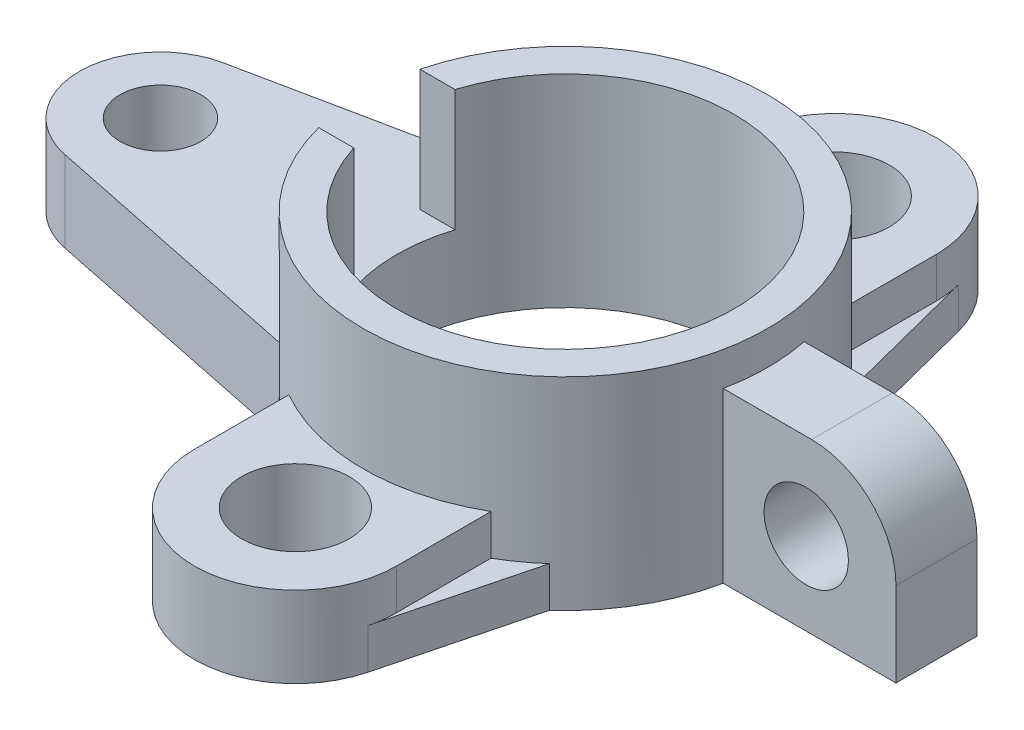
SolidWorks part; units mm, degrees
ref_plane "Ön Düzlem" through (0, 0, 0) normal (0, 0, 1) x (1, 0, 0)
ref_plane "Üst Düzlem" through (0, 0, 0) normal (0, 1, 0) x (1, 0, 0)
ref_plane "Sağ Düzlem" through (0, 0, 0) normal (1, 0, 0) x (0, 0, -1)
sketch "Çizim1" plane through (0, 0, 0) normal (0, 1, 0) x (1, 0, 0)
  line L0 (0, 0) -> (0, 40) construction
  line L1 (0, 40) -> (0, 0) construction
  line L2 (0, 0) -> (-60, 0) construction
  line L3 (-62.4196, 11.7535) -> (-22.3607, 20)
  line L4 (-62.4196, -11.7535) -> (-22.3607, -20)
  line L5 (-29.0474, 7.5) -> (-23.8485, 7.5)
  line L6 (-29.0474, -7.5) -> (-23.8485, -7.5)
  line L7 (0, 40) -> (-14.9787, 40) construction
  line L8 (-14.9787, 40) -> (-14.9787, 25.993)
  line L9 (14.9787, 40) -> (14.9787, 25.993)
  line L10 (-14.5071, 43.7291) -> (-20, 22.3607)
  line L11 (14.5071, 43.7291) -> (20, 22.3607)
  line L12 (14.5071, -43.7291) -> (20, -22.3607)
  line L13 (14.9787, -40) -> (14.9787, -25.993)
  line L14 (-14.9787, -40) -> (-14.9787, -25.993)
  line L15 (-14.5071, -43.7291) -> (-20, -22.3607)
  line L16 (30, 0) -> (55, 0) construction
  line L17 (55, -6) -> (55, 6)
  line L18 (55, 6) -> (29.3939, 6)
  line L19 (55, -6) -> (29.3939, -6)
  arc A0 (-29.0474, -7.5) -> (-29.0474, 7.5) centre (0, 0) ccw
  circle A1 centre (0, 0) radius 25
  circle A2 centre (-60, 0) radius 6
  arc A3 (-62.4196, 11.7535) -> (-62.4196, -11.7535) centre (-60, 0) ccw
  arc A4 (-14.9787, 40) -> (14.9787, 40) centre (0, 40) cw
  circle A5 centre (0, 40) radius 7.9877
  circle A6 centre (0, -40) radius 7.9877
  arc A7 (-14.9787, -40) -> (14.9787, -40) centre (0, -40) ccw
  dimension "D1" = 60
  dimension "D2" = 50
  dimension "D3" = 12
  dimension "D4" = 12
  dimension "D6" = 60
  dimension "D5" = 40
  dimension "D7" = 15
  dimension "D8" = 40
  dimension "D9" = 80
  dimension "D10" = 12
  dimension "D11" = 55
extrude "Yükseklik-Ekstrüzyon2" add sketch "Çizim1" along normal blind 30 contours A1 L6 A0 L5 region at (-20.6179, 0, -20.6179)
extrude "Yükseklik-Ekstrüzyon3" add sketch "Çizim1<7>" along normal blind 12 contours L3 A3 L4 A0 L6 A1 L5 A2 | A7 L13 A0 L14 A6 | A4 L8 A0 L9 A5 region at (-44.2699, 0, 0) region at (0, 0, -54.5619) region at (-14.4468, 0, 41.8271)
sketch "Çizim1<7>" plane through (0, 0, 0) normal (0, 1, 0) x (1, 0, 0) same geometry as "Çizim1"
extrude "Yükseklik-Ekstrüzyon6" add sketch "Çizim1<12>" along normal blind 6 contours L8 A4 L10 A0 | A7 L14 A0 L15 | A7 L12 A0 L13 | L11 A4 L9 A0 region at (-16.631, 0, -30.2261) region at (-16.631, 0, 30.2261) region at (16.631, 0, -30.2261) region at (16.631, 0, 30.2261)
sketch "Çizim1<12>" plane through (0, 0, 0) normal (0, 1, 0) x (1, 0, 0) same geometry as "Çizim1"
extrude "Yükseklik-Ekstrüzyon7" add sketch "Çizim1<13>" along normal blind 25 contours A0 L19 L17 L18 region at (42.3987, 0, 0)
sketch "Çizim1<13>" plane through (0, 0, 0) normal (0, 1, 0) x (1, 0, 0) same geometry as "Çizim1"
fillet "Radyus1" radius 12.5 1 edges at (55, 25, 0)
sketch "Çizim2" plane through (0, 0, 6) normal (0, 0, 1) x (1, 0, 0)
  circle A0 centre (41.6984, 12.2001) radius 6.25
  point P2 (0, 0)
  point P3 (0, 0)
  dimension "D1" = 12.5
extrude "Kes-Ekstrüzyon1" cut sketch "Çizim2" against normal through all contours A0
